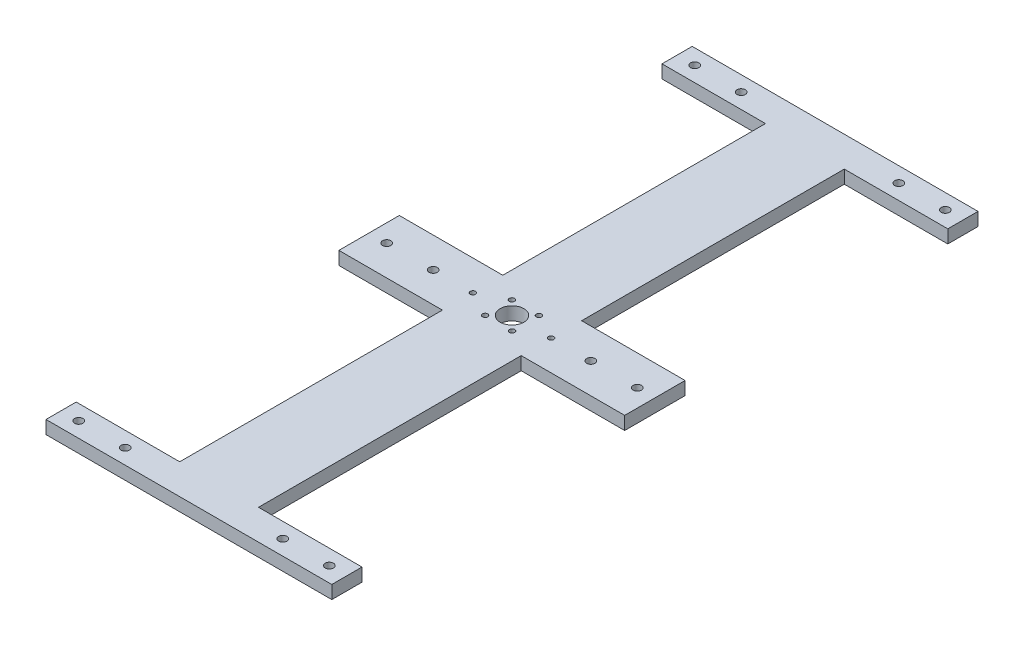
SolidWorks part; units mm, degrees
ref_plane "Front Plane" through (0, 0, 0) normal (0, 0, 1) x (1, 0, 0)
ref_plane "Top Plane" through (0, 0, 0) normal (0, 1, 0) x (1, 0, 0)
ref_plane "Right Plane" through (0, 0, 0) normal (1, 0, 0) x (0, 0, -1)
sketch "Sketch1" plane through (0, 0, 0) normal (0, 1, 0) x (1, 0, 0)
  line L1 (0, 0) -> (108.8, 0)
  line L2 (0, 0) -> (0, 23)
  line L3 (0, 23) -> (108.8, 23)
  line L4 (108.8, 0) -> (108.8, 23)
  dimension "D1" = 108.8
  dimension "D2" = 23
extrude "Mount Base" add sketch "Sketch1" along normal blind 5
sketch "Sketch2" plane through (0, 5, 0) normal (0, 1, 0) x (1, 0, 0)
  line L0 (108.8, 0) -> (108.8, 23) construction
  line L1 (0, 0) -> (108.8, 0) construction
  circle A0 centre (59.55, 16.6) radius 1
  circle A1 centre (59.55, 6.4) radius 1
  circle A2 centre (49.25, 6.4) radius 1
  circle A3 centre (49.25, 16.6) radius 1
  circle A4 centre (69.31, 11.5) radius 1
  circle A5 centre (39.49, 11.5) radius 1
  circle A6 centre (54.4, 11.5) radius 4.5
  point P16 (108.8, 11.5)
  point P19 (54.4, 0)
  dimension "D4" = 9
  dimension "D1" = 2
  dimension "D3" = 10.3
  dimension "D5" = 5.15
  dimension "D6" = 5.1
  dimension "D2" = 10.2
  dimension "D7" = 14.91
  dimension "D8" = 14.91
extrude "Bracket Screw Holes" cut sketch "Sketch2" against normal up to surface (5 mm away) up to face at (54.4, 0, -11.5)
sketch "Sketch3" plane through (0, 5, 0) normal (0, 1, 0) x (1, 0, 0)
  line L0 (0, 23) -> (0, 0) construction
  circle A0 centre (6.7, 11.5) radius 1.5875
  circle A1 centre (24.4, 11.5) radius 1.5875
  circle A2 centre (84.4, 11.5) radius 1.5875
  circle A3 centre (102.1, 11.5) radius 1.5875
  circle A4 centre (54.4, 11.5) radius 4.5 construction
  point P13 (0, 11.5)
  dimension "D1" = 3.175
  dimension "D2" = 17.7
  dimension "D3" = 17.7
  dimension "D4" = 30
  dimension "D5" = 30
extrude "Antenna Screw Holes" cut sketch "Sketch3" against normal up to surface (5 mm away) up to face at (59.55, 0, -7.4)
sketch "Sketch6" plane through (0, 0, -23) normal (0, 0, -1) x (-1, 0, 0)
  line L0 (-108.8, 5) -> (0, 5) construction
  line L1 (-39.4, 5) -> (-69.4, 5)
  line L2 (-39.4, 5) -> (-39.4, 0)
  line L3 (-39.4, 0) -> (-69.4, 0)
  line L4 (-69.4, 5) -> (-69.4, 0)
  line L5 (-108.8, 0) -> (0, 0) construction
  point P8 (0, 0)
  point P9 (-54.4, 5)
  point P10 (-54.4, 5)
  dimension "D1" = 30
extrude "Director Extension" add sketch "Sketch6" along normal blind 100
sketch "Sketch7" plane through (0, 0, -123) normal (0, 0, -1) x (-1, 0, 0)
  line L0 (-108.8, 5) -> (-108.8, 0) construction
  line L1 (-108.8, 5) -> (0, 5)
  line L2 (-108.8, 5) -> (-108.8, 0)
  line L3 (-108.8, 0) -> (0, 0)
  line L4 (0, 5) -> (0, 0)
  point P4 (0, 0)
extrude "Director Mount" add sketch "Sketch7" along normal blind 11.5
sketch "Sketch10" plane through (0, 0, 0) normal (0, 0, 1) x (1, 0, 0)
  line L0 (0, 5) -> (108.8, 5) construction
  line L1 (39.4, 5) -> (69.4, 5)
  line L2 (39.4, 5) -> (39.4, 0)
  line L3 (39.4, 0) -> (69.4, 0)
  line L4 (69.4, 5) -> (69.4, 0)
  line L5 (0, 0) -> (108.8, 0) construction
  point P8 (0, 0)
extrude "Reflector Extension" add sketch "Sketch10" along normal blind 100
sketch "Sketch11" plane through (0, 0, 100) normal (0, 0, 1) x (1, 0, 0)
  line L0 (108.8, 5) -> (108.8, 0) construction
  line L1 (0, 5) -> (108.8, 5)
  line L2 (0, 5) -> (0, 0)
  line L3 (0, 0) -> (108.8, 0)
  line L4 (108.8, 5) -> (108.8, 0)
  point P4 (0, 0)
extrude "Reflector Mount" add sketch "Sketch11" along normal blind 11.5
pattern_linear "LPattern1" count 2 spacing 117.25 along (0, 0, 1) count 2 spacing 117.25 along (0, 0, -1) of "Antenna Screw Holes" pattern seed only yes
equation "\"D8@Sketch2\"=\"D7@Sketch2\""
equation "\"D7@Sketch2\"=8.76+\"D3@Sketch2\"/2 + \"D1@Sketch2\"/2"
equation "\"D6@Sketch2\"=\"D2@Sketch2\"/2"
equation "\"D5@Sketch2\"=\"D3@Sketch2\"/2"
equation "\"D3@Sketch3\"=\"D2@Sketch3\""
equation "\"D5@Sketch3\"=\"D4@Sketch3\""
equation "\"MountWidth\"=23"
equation "\"D2@Sketch1\"=\"MountWidth\""
equation "\"D1@Director Mount\" = \"MountWidth\" / 2"
equation "\"ExtensionLength\"=100"
equation "\"D1@Director Extension\"=\"ExtensionLength\""
equation "\"D1@Reflector Extension\"=\"ExtensionLength\""
equation "\"D1@Reflector Mount\" = \"MountWidth\" / 2"
equation "\"D4@LPattern1\"=\"ExtensionLength\"+\"MountWidth\"*3/4"
equation "\"D3@LPattern1\"=\"ExtensionLength\"+\"MountWidth\"*3/4"
